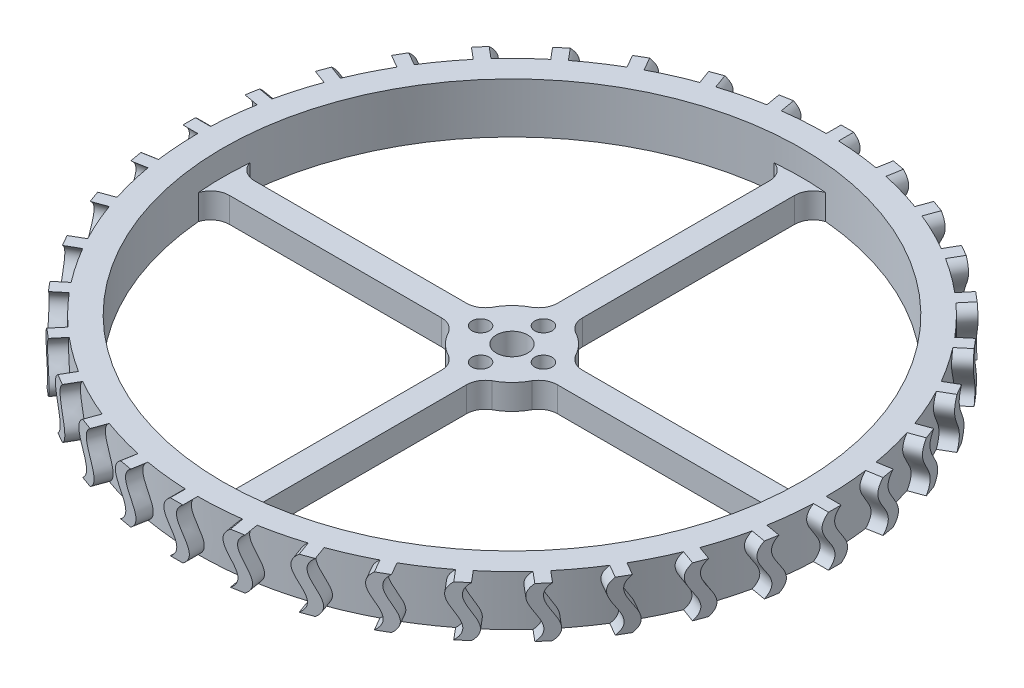
SolidWorks part; units mm, degrees
ref_plane "Front Plane" through (0, 0, 0) normal (0, 0, 1) x (1, 0, 0)
ref_plane "Top Plane" through (0, 0, 0) normal (0, 1, 0) x (1, 0, 0)
ref_plane "Right Plane" through (0, 0, 0) normal (1, 0, 0) x (0, 0, -1)
sketch "Sketch2" plane through (0, 0, 0) normal (0, 1, 0) x (1, 0, 0)
  line L0 (9.525, 0) -> (58.42, 0)
  line L1 (9.1801, 2.54) -> (58.3648, 2.54)
  line L2 (9.1801, -2.54) -> (58.3648, -2.54)
  line L3 (2.54, -9.1801) -> (2.54, -58.3648)
  line L4 (-2.54, -9.1801) -> (-2.54, -58.3648)
  line L5 (-9.1801, -2.54) -> (-58.3648, -2.54)
  line L6 (-9.1801, 2.54) -> (-58.3648, 2.54)
  line L7 (-2.54, 9.1801) -> (-2.54, 58.3648)
  line L8 (2.54, 9.1801) -> (2.54, 58.3648)
  circle A0 centre (0, 0) radius 9.525
  circle A1 centre (6.35, 0) radius 1.75
  circle A2 centre (0, 0) radius 3.175
  circle A3 centre (0, 0) radius 63.5
  circle A4 centre (0, 0) radius 58.42
  arc A5 (11.7201, -2.54) -> (8.4538, -4.3886) centre (11.7201, -6.35) ccw
  arc A6 (11.7201, 2.54) -> (8.4538, 4.3886) centre (11.7201, 6.35) cw
  arc A7 (54.5548, -2.54) -> (58.1879, -5.2026) centre (54.5548, -6.35) cw
  arc A8 (54.5548, 2.54) -> (58.1879, 5.2026) centre (54.5548, 6.35) ccw
  circle A9 centre (0, -6.35) radius 1.75
  arc A10 (-2.54, -11.7201) -> (-4.3886, -8.4538) centre (-6.35, -11.7201) ccw
  arc A11 (2.54, -11.7201) -> (4.3886, -8.4538) centre (6.35, -11.7201) cw
  arc A12 (-2.54, -54.5548) -> (-5.2026, -58.1879) centre (-6.35, -54.5548) cw
  arc A13 (2.54, -54.5548) -> (5.2026, -58.1879) centre (6.35, -54.5548) ccw
  circle A14 centre (-6.35, 0) radius 1.75
  arc A15 (-11.7201, 2.54) -> (-8.4538, 4.3886) centre (-11.7201, 6.35) ccw
  arc A16 (-11.7201, -2.54) -> (-8.4538, -4.3886) centre (-11.7201, -6.35) cw
  arc A17 (-54.5548, 2.54) -> (-58.1879, 5.2026) centre (-54.5548, 6.35) cw
  arc A18 (-54.5548, -2.54) -> (-58.1879, -5.2026) centre (-54.5548, -6.35) ccw
  circle A19 centre (0, 6.35) radius 1.75
  arc A20 (2.54, 11.7201) -> (4.3886, 8.4538) centre (6.35, 11.7201) ccw
  arc A21 (-2.54, 11.7201) -> (-4.3886, 8.4538) centre (-6.35, 11.7201) cw
  arc A22 (2.54, 54.5548) -> (5.2026, 58.1879) centre (6.35, 54.5548) cw
  arc A23 (-2.54, 54.5548) -> (-5.2026, 58.1879) centre (-6.35, 54.5548) ccw
  dimension "D1" = 3.5
  dimension "D3" = 19.05
  dimension "D4" = 127
  dimension "D5" = 2.54
  dimension "D2" = 6.35
  dimension "D6" = 2.54
  dimension "D7" = 2.54
  dimension "D8" = 3.81
  dimension "D9" = 3.81
  dimension "D10" = 2.54
  dimension "D11" = 3.81
  dimension "D12" = 3.81
  dimension "D13" = 3.81
  dimension "D14" = 3.81
  dimension "D15" = 4
extrude "Boss-Extrude3" add sketch "Sketch2" along normal blind 5.08 contours L4 A12 A4 | A13 L3 A4 | L4 A4 L3 A0 | L2 A4 L0 A0 | L0 A4 L1 A0 | L8 A4 L7 A0 | L6 A4 L5 A0 | A0 A19 A14 A9 A2 A1 | L2 A7 A4 | A8 L1 A4 | L3 A11 A0 | A5 L2 A0 | A10 L4 A0 | L5 A16 A0 | A20 L8 A0 | L1 A6 A0 | L7 A21 A0 | A15 L6 A0 | A18 L5 A4 | L6 A17 A4 | L8 A22 A4 | A23 L7 A4 region at (33.9061, 0, -1.2712) region at (9.1714, 0, 1.2454) region at (33.9061, 0, 1.2712) region at (9.5984, 0, -2.9699) region at (9.5984, 0, 2.9699) region at (57.4365, 0, -3.2695) region at (57.4365, 0, 3.2695) region at (2.9699, 0, -9.5984) region at (2.9699, 0, 9.5984) region at (3.2695, 0, -57.4365) region at (3.2695, 0, 57.4365) region at (0, 0, -33.9061) region at (0, 0, 33.9061) region at (-2.9699, 0, -9.5984) region at (-2.9699, 0, 9.5984) region at (-3.2695, 0, -57.4365) region at (-3.2695, 0, 57.4365) region at (-9.5984, 0, -2.9699) region at (-9.5984, 0, 2.9699) region at (-57.4365, 0, -3.2695) region at (-57.4365, 0, 3.2695) region at (-33.9061, 0, 0)
extrude "Boss-Extrude4" add sketch "Sketch2<3>" along normal blind 10.16 contours A3 A4 region at (-61.7039, 0, 0)
sketch "Sketch2<3>" plane through (0, 0, 0) normal (0, 1, 0) x (1, 0, 0) same geometry as "Sketch2"
sketch "Sketch3" plane through (0, 0, 0) normal (0, -1, 0) x (1, 0, 0)
  line L0 (0, 0) -> (0, 63.5)
  line L1 (0, 63.5) -> (-64.9401, 63.5)
  circle A0 centre (0, 0) radius 63.5 construction
sketch "Sketch4" plane through (0, 5.08, 0) normal (0, 1, 0) x (1, 0, 0)
  line L0 (0, 0) -> (0, -63.5)
ref_plane "Plane1" through (0, 0, 63.5) normal (0, 0, -1) x (-1, 0, 0)
sketch "Sketch5" plane through (0, 0, 63.5) normal (0, 0, -1) x (-1, 0, 0)
  line L0 (0, 0) -> (0, 10.16)
  line L1 (63.5, 10.16) -> (-63.5, 10.16) construction
  line L2 (0, 2.54) -> (-1.27, 2.54)
  line L3 (0, 7.62) -> (1.27, 7.62)
  line L4 (0, 0) -> (2.54, 0)
  line L5 (2.54, 10.16) -> (0, 10.16)
  line L6 (0, 10.16) -> (2.54, 10.16)
  line L7 (2.54, 0) -> (0, 0)
  spline S0 degree 3 poles (0, 0) (-2.2578, 1.6933) (0, 5.08) (2.2578, 8.4667) (0, 10.16) knots 0 0 0 0 0.5 1 1 1 1
  spline S1 degree 3 poles (2.54, 0) (0.2822, 1.6933) (2.54, 5.08) (4.7978, 8.4667) (2.54, 10.16) knots 0 0 0 0 0.5 1 1 1 1
  dimension "D1" = 2.54
  dimension "D2" = 2.54
  dimension "D3" = 1.27
  dimension "D4" = 1.27
extrude "Boss-Extrude5" add sketch "Sketch5" against normal blind 3 and the other way blind 2 contours L4 S1 L5 S0 L0 | S0 L2 L0 | S0 L0 L2 region at (0.5528, 1.5428, 63.5) region at (-1.6272, 5.6219, 63.5) region at (0.4688, 3.435, 63.5)
ref_axis "Axis2" through (0, 0, 0) along (0, 1, 0)
pattern_circular "CirPattern1" count 36 over 360 about axis through (0, 0, 0) along (0, 1, 0) of "Boss-Extrude5"
